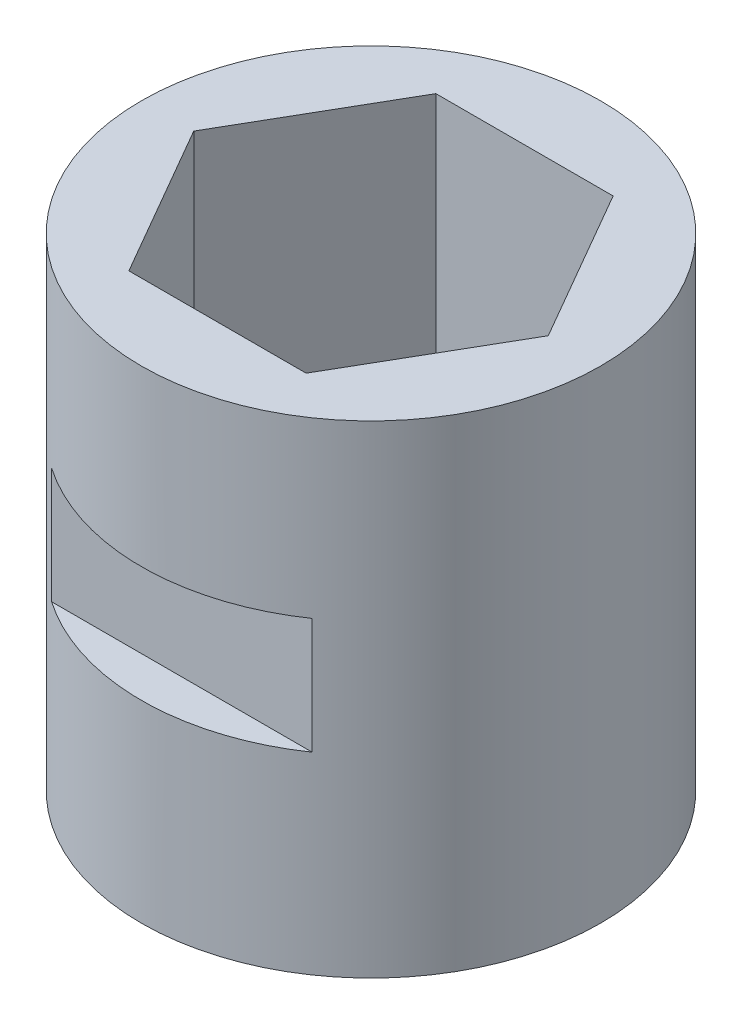
SolidWorks part; units mm, degrees
material "Polyester Resin"
ref_plane "Front Plane" through (0, 0, 0) normal (0, 0, 1) x (1, 0, 0)
ref_plane "Top Plane" through (0, 0, 0) normal (0, 1, 0) x (1, 0, 0)
ref_plane "Right Plane" through (0, 0, 0) normal (1, 0, 0) x (0, 0, -1)
sketch "Sketch1" plane through (0, 0, 0) normal (0, 1, 0) x (1, 0, 0)
  line L1 (-2.9156, 5.05) -> (-5.8312, 0)
  line L2 (-5.8312, 0) -> (-2.9156, -5.05)
  line L3 (-2.9156, -5.05) -> (2.9156, -5.05)
  line L4 (2.9156, -5.05) -> (5.8312, 0)
  line L5 (5.8312, 0) -> (2.9156, 5.05)
  line L6 (2.9156, 5.05) -> (-2.9156, 5.05)
  circle A0 centre (0, 0) radius 5.05 construction
  circle A1 centre (0, 0) radius 7.5565
  dimension "D2" = 15.113
  dimension "D1" = 10.1
extrude "Boss-Extrude1" add sketch "Sketch1" along normal blind 12.7
sketch "Sketch2" plane through (0, 0, 0) normal (0, -1, 0) x (1, 0, 0)
  circle A0 centre (0, 0) radius 7.5565
  circle A1 centre (0, 0) radius 3.3
  dimension "D1" = 6.6
extrude "Boss-Extrude2" add sketch "Sketch2" along normal blind 3.175
sketch "Sketch3" plane through (0, 0, 0) normal (1, 0, 0) x (0, 0, -1)
  line L0 (-6.223, 6.985) -> (-6.223, 3.175)
  line L1 (6.223, 6.985) -> (6.223, 3.175)
  line L2 (-7.5565, -3.175) -> (7.5565, -3.175) construction
  line L3 (-6.223, 6.985) -> (-8.202, 6.985)
  line L4 (-8.202, 6.985) -> (-8.202, 3.175)
  line L5 (-8.202, 3.175) -> (-6.223, 3.175)
  line L6 (6.223, 6.985) -> (8.4791, 6.985)
  line L7 (8.4791, 6.985) -> (8.4791, 3.175)
  line L8 (8.4791, 3.175) -> (6.223, 3.175)
  dimension "D1" = 12.446
  dimension "D2" = 6.223
  dimension "D3" = 3.81
  dimension "D4" = 3.81
  dimension "D5" = 6.35
  dimension "D6" = 6.35
extrude "Cut-Extrude1" cut sketch "Sketch3" against normal through all and the other way through all
equation "\"AB_Central_Bushing_Length\" = .75in"
equation "\"Solid_Length\"= .125in"
equation "\"Hex_Length\" = .5"
equation "\"D1@Boss-Extrude1\"= \"Hex_Length\""
equation "\"D1@Boss-Extrude2\"=\"Solid_Length\""
equation "\"Cutout_Angle\" = 80"
